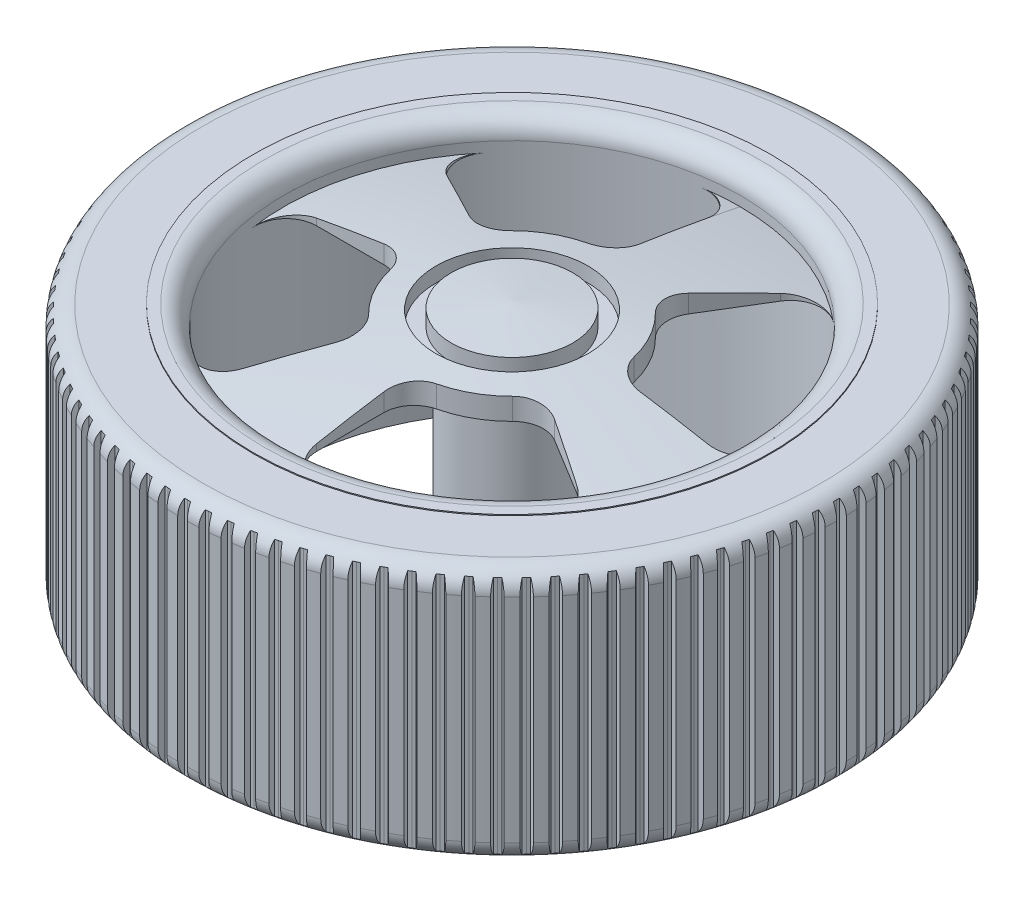
SolidWorks part; units mm, degrees
ref_plane "Ön Düzlem" through (0, 0, 0) normal (0, 0, 1) x (1, 0, 0)
ref_plane "Üst Düzlem" through (0, 0, 0) normal (0, 1, 0) x (1, 0, 0)
ref_plane "Sağ Düzlem" through (0, 0, 0) normal (1, 0, 0) x (0, 0, -1)
sketch "Çizim1" plane through (0, 0, 0) normal (0, 1, 0) x (1, 0, 0)
  circle A0 centre (0, 0) radius 32.5
  circle A1 centre (0, 0) radius 25.5
  dimension "D1" = 65
  dimension "D2" = 51
extrude "Yükseklik-Ekstrüzyon1" add sketch "Çizim1" along normal blind 12.5 and the other way blind 12.5
fillet "Radyus2" radius 2 2 edges at (0, 12.5, 32.5) (0, -12.5, 32.5)
sketch "Çizim2" plane through (0, 0, 0) normal (0, 1, 0) x (1, 0, 0)
  line L0 (0, 0) -> (0, 32) construction
  line L1 (0, 32) -> (-0.3, 31.9986)
  line L2 (-0.3, 31.9986) -> (-0.5822, 32.8175)
  line L3 (-0.5822, 32.8175) -> (0.5822, 32.8175)
  line L5 (0, 32) -> (0.3, 31.9986)
  line L6 (0.3, 31.9986) -> (0.5822, 32.8175)
  line L7 (2.0093, 31.9369) -> (2.3086, 31.9166)
  line L8 (2.3086, 31.9166) -> (2.6417, 32.7162)
  line L9 (1.4796, 32.7893) -> (2.6417, 32.7162)
  line L10 (1.7098, 31.9543) -> (1.4796, 32.7893)
  line L11 (2.0093, 31.9369) -> (1.7098, 31.9543)
  line L12 (4.0107, 31.7477) -> (4.3081, 31.7087)
  line L13 (4.3081, 31.7087) -> (4.6907, 32.4858)
  line L14 (3.5355, 32.6317) -> (4.6907, 32.4858)
  line L15 (3.7129, 31.7839) -> (3.5355, 32.6317)
  line L16 (4.0107, 31.7477) -> (3.7129, 31.7839)
  line L17 (5.9962, 31.4332) -> (6.2906, 31.3756)
  line L18 (6.2906, 31.3756) -> (6.7213, 32.1271)
  line L19 (5.5775, 32.3453) -> (6.7213, 32.1271)
  line L20 (5.7013, 31.488) -> (5.5775, 32.3453)
  line L21 (5.9962, 31.4332) -> (5.7013, 31.488)
  line L22 (7.9581, 30.9947) -> (8.2483, 30.9187)
  line L23 (8.2483, 30.9187) -> (8.7253, 31.6417)
  line L24 (7.5975, 31.9313) -> (8.7253, 31.6417)
  line L25 (7.6672, 31.0679) -> (7.5975, 31.9313)
  line L26 (7.9581, 30.9947) -> (7.6672, 31.0679)
  line L27 (9.8885, 30.4338) -> (10.1734, 30.3398)
  line L28 (10.1734, 30.3398) -> (10.6949, 31.0314)
  line L29 (9.5875, 31.3912) -> (10.6949, 31.0314)
  line L30 (9.6028, 30.5252) -> (9.5875, 31.3912)
  line L31 (9.8885, 30.4338) -> (9.6028, 30.5252)
  line L32 (11.78, 29.7528) -> (12.0584, 29.6411)
  line L33 (12.0584, 29.6411) -> (12.6222, 30.2986)
  line L34 (11.5396, 30.7273) -> (12.6222, 30.2986)
  line L35 (11.5005, 29.862) -> (11.5396, 30.7273)
  line L36 (11.78, 29.7528) -> (11.5005, 29.862)
  line L37 (13.6249, 28.9545) -> (13.8958, 28.8255)
  line L38 (13.8958, 28.8255) -> (14.4998, 29.4463)
  line L39 (13.4462, 29.942) -> (14.4998, 29.4463)
  line L40 (13.3529, 29.0809) -> (13.4462, 29.942)
  line L41 (13.6249, 28.9545) -> (13.3529, 29.0809)
  line L42 (15.4161, 28.0418) -> (15.6783, 27.8961)
  line L43 (15.6783, 27.8961) -> (16.3201, 28.4777)
  line L44 (15.2998, 29.0387) -> (16.3201, 28.4777)
  line L45 (15.1525, 28.1851) -> (15.2998, 29.0387)
  line L46 (15.4161, 28.0418) -> (15.1525, 28.1851)
  line L47 (17.1465, 27.0185) -> (17.399, 26.8566)
  line L48 (17.399, 26.8566) -> (18.0761, 27.3968)
  line L49 (17.0929, 28.0207) -> (18.0761, 27.3968)
  line L50 (16.8924, 27.1781) -> (17.0929, 28.0207)
  line L51 (17.1465, 27.0185) -> (16.8924, 27.1781)
  line L52 (18.8091, 25.8885) -> (19.051, 25.7111)
  line L53 (19.051, 25.7111) -> (19.7606, 26.2077)
  line L54 (18.8186, 26.8921) -> (19.7606, 26.2077)
  line L55 (18.5656, 26.0637) -> (18.8186, 26.8921)
  line L56 (18.8091, 25.8885) -> (18.5656, 26.0637)
  line L57 (20.3976, 24.6564) -> (20.6278, 24.4641)
  line L58 (20.6278, 24.4641) -> (21.3672, 24.9152)
  line L59 (20.4701, 25.6574) -> (21.3672, 24.9152)
  line L60 (20.1655, 24.8466) -> (20.4701, 25.6574)
  line L61 (20.3976, 24.6564) -> (20.1655, 24.8466)
  line L62 (21.9055, 23.327) -> (22.1232, 23.1206)
  line L63 (22.1232, 23.1206) -> (22.8895, 23.5244)
  line L64 (22.0407, 24.3215) -> (22.8895, 23.5244)
  line L65 (21.6859, 23.5313) -> (22.0407, 24.3215)
  line L66 (21.9055, 23.327) -> (21.6859, 23.5313)
  line L67 (23.327, 21.9055) -> (23.5313, 21.6859)
  line L68 (23.5313, 21.6859) -> (24.3215, 22.0407)
  line L69 (23.5244, 22.8895) -> (24.3215, 22.0407)
  line L70 (23.1206, 22.1232) -> (23.5244, 22.8895)
  line L71 (23.327, 21.9055) -> (23.1206, 22.1232)
  line L72 (24.6564, 20.3976) -> (24.8466, 20.1655)
  line L73 (24.8466, 20.1655) -> (25.6574, 20.4701)
  line L74 (24.9152, 21.3672) -> (25.6574, 20.4701)
  line L75 (24.4641, 20.6278) -> (24.9152, 21.3672)
  line L76 (24.6564, 20.3976) -> (24.4641, 20.6278)
  line L77 (25.8885, 18.8091) -> (26.0637, 18.5656)
  line L78 (26.0637, 18.5656) -> (26.8921, 18.8186)
  line L79 (26.2077, 19.7606) -> (26.8921, 18.8186)
  line L80 (25.7111, 19.051) -> (26.2077, 19.7606)
  line L81 (25.8885, 18.8091) -> (25.7111, 19.051)
  line L82 (27.0185, 17.1465) -> (27.1781, 16.8924)
  line L83 (27.1781, 16.8924) -> (28.0207, 17.0929)
  line L84 (27.3968, 18.0761) -> (28.0207, 17.0929)
  line L85 (26.8566, 17.399) -> (27.3968, 18.0761)
  line L86 (27.0185, 17.1465) -> (26.8566, 17.399)
  line L87 (28.0418, 15.4161) -> (28.1851, 15.1525)
  line L88 (28.1851, 15.1525) -> (29.0387, 15.2998)
  line L89 (28.4777, 16.3201) -> (29.0387, 15.2998)
  line L90 (27.8961, 15.6783) -> (28.4777, 16.3201)
  line L91 (28.0418, 15.4161) -> (27.8961, 15.6783)
  line L92 (28.9545, 13.6249) -> (29.0809, 13.3529)
  line L93 (29.0809, 13.3529) -> (29.942, 13.4462)
  line L94 (29.4463, 14.4998) -> (29.942, 13.4462)
  line L95 (28.8255, 13.8958) -> (29.4463, 14.4998)
  line L96 (28.9545, 13.6249) -> (28.8255, 13.8958)
  line L97 (29.7528, 11.78) -> (29.862, 11.5005)
  line L98 (29.862, 11.5005) -> (30.7273, 11.5396)
  line L99 (30.2986, 12.6222) -> (30.7273, 11.5396)
  line L100 (29.6411, 12.0584) -> (30.2986, 12.6222)
  line L101 (29.7528, 11.78) -> (29.6411, 12.0584)
  line L102 (30.4338, 9.8885) -> (30.5252, 9.6028)
  line L103 (30.5252, 9.6028) -> (31.3912, 9.5875)
  line L104 (31.0314, 10.6949) -> (31.3912, 9.5875)
  line L105 (30.3398, 10.1734) -> (31.0314, 10.6949)
  line L106 (30.4338, 9.8885) -> (30.3398, 10.1734)
  line L107 (30.9947, 7.9581) -> (31.0679, 7.6672)
  line L108 (31.0679, 7.6672) -> (31.9313, 7.5975)
  line L109 (31.6417, 8.7253) -> (31.9313, 7.5975)
  line L110 (30.9187, 8.2483) -> (31.6417, 8.7253)
  line L111 (30.9947, 7.9581) -> (30.9187, 8.2483)
  line L112 (31.4332, 5.9962) -> (31.488, 5.7013)
  line L113 (31.488, 5.7013) -> (32.3453, 5.5775)
  line L114 (32.1271, 6.7213) -> (32.3453, 5.5775)
  line L115 (31.3756, 6.2906) -> (32.1271, 6.7213)
  line L116 (31.4332, 5.9962) -> (31.3756, 6.2906)
  line L117 (31.7477, 4.0107) -> (31.7839, 3.7129)
  line L118 (31.7839, 3.7129) -> (32.6317, 3.5355)
  line L119 (32.4858, 4.6907) -> (32.6317, 3.5355)
  line L120 (31.7087, 4.3081) -> (32.4858, 4.6907)
  line L121 (31.7477, 4.0107) -> (31.7087, 4.3081)
  line L122 (31.9369, 2.0093) -> (31.9543, 1.7098)
  line L123 (31.9543, 1.7098) -> (32.7893, 1.4796)
  line L124 (32.7162, 2.6417) -> (32.7893, 1.4796)
  line L125 (31.9166, 2.3086) -> (32.7162, 2.6417)
  line L126 (31.9369, 2.0093) -> (31.9166, 2.3086)
  line L127 (32, 0) -> (31.9986, -0.3)
  line L128 (31.9986, -0.3) -> (32.8175, -0.5822)
  line L129 (32.8175, 0.5822) -> (32.8175, -0.5822)
  line L130 (31.9986, 0.3) -> (32.8175, 0.5822)
  line L131 (32, 0) -> (31.9986, 0.3)
  line L132 (31.9369, -2.0093) -> (31.9166, -2.3086)
  line L133 (31.9166, -2.3086) -> (32.7162, -2.6417)
  line L134 (32.7893, -1.4796) -> (32.7162, -2.6417)
  line L135 (31.9543, -1.7098) -> (32.7893, -1.4796)
  line L136 (31.9369, -2.0093) -> (31.9543, -1.7098)
  line L137 (31.7477, -4.0107) -> (31.7087, -4.3081)
  line L138 (31.7087, -4.3081) -> (32.4858, -4.6907)
  line L139 (32.6317, -3.5355) -> (32.4858, -4.6907)
  line L140 (31.7839, -3.7129) -> (32.6317, -3.5355)
  line L141 (31.7477, -4.0107) -> (31.7839, -3.7129)
  line L142 (31.4332, -5.9962) -> (31.3756, -6.2906)
  line L143 (31.3756, -6.2906) -> (32.1271, -6.7213)
  line L144 (32.3453, -5.5775) -> (32.1271, -6.7213)
  line L145 (31.488, -5.7013) -> (32.3453, -5.5775)
  line L146 (31.4332, -5.9962) -> (31.488, -5.7013)
  line L147 (30.9947, -7.9581) -> (30.9187, -8.2483)
  line L148 (30.9187, -8.2483) -> (31.6417, -8.7253)
  line L149 (31.9313, -7.5975) -> (31.6417, -8.7253)
  line L150 (31.0679, -7.6672) -> (31.9313, -7.5975)
  line L151 (30.9947, -7.9581) -> (31.0679, -7.6672)
  line L152 (30.4338, -9.8885) -> (30.3398, -10.1734)
  line L153 (30.3398, -10.1734) -> (31.0314, -10.6949)
  line L154 (31.3912, -9.5875) -> (31.0314, -10.6949)
  line L155 (30.5252, -9.6028) -> (31.3912, -9.5875)
  line L156 (30.4338, -9.8885) -> (30.5252, -9.6028)
  line L157 (29.7528, -11.78) -> (29.6411, -12.0584)
  line L158 (29.6411, -12.0584) -> (30.2986, -12.6222)
  line L159 (30.7273, -11.5396) -> (30.2986, -12.6222)
  line L160 (29.862, -11.5005) -> (30.7273, -11.5396)
  line L161 (29.7528, -11.78) -> (29.862, -11.5005)
  line L162 (28.9545, -13.6249) -> (28.8255, -13.8958)
  line L163 (28.8255, -13.8958) -> (29.4463, -14.4998)
  line L164 (29.942, -13.4462) -> (29.4463, -14.4998)
  line L165 (29.0809, -13.3529) -> (29.942, -13.4462)
  line L166 (28.9545, -13.6249) -> (29.0809, -13.3529)
  line L167 (28.0418, -15.4161) -> (27.8961, -15.6783)
  line L168 (27.8961, -15.6783) -> (28.4777, -16.3201)
  line L169 (29.0387, -15.2998) -> (28.4777, -16.3201)
  line L170 (28.1851, -15.1525) -> (29.0387, -15.2998)
  line L171 (28.0418, -15.4161) -> (28.1851, -15.1525)
  line L172 (27.0185, -17.1465) -> (26.8566, -17.399)
  line L173 (26.8566, -17.399) -> (27.3968, -18.0761)
  line L174 (28.0207, -17.0929) -> (27.3968, -18.0761)
  line L175 (27.1781, -16.8924) -> (28.0207, -17.0929)
  line L176 (27.0185, -17.1465) -> (27.1781, -16.8924)
  line L177 (25.8885, -18.8091) -> (25.7111, -19.051)
  line L178 (25.7111, -19.051) -> (26.2077, -19.7606)
  line L179 (26.8921, -18.8186) -> (26.2077, -19.7606)
  line L180 (26.0637, -18.5656) -> (26.8921, -18.8186)
  line L181 (25.8885, -18.8091) -> (26.0637, -18.5656)
  line L182 (24.6564, -20.3976) -> (24.4641, -20.6278)
  line L183 (24.4641, -20.6278) -> (24.9152, -21.3672)
  line L184 (25.6574, -20.4701) -> (24.9152, -21.3672)
  line L185 (24.8466, -20.1655) -> (25.6574, -20.4701)
  line L186 (24.6564, -20.3976) -> (24.8466, -20.1655)
  line L187 (23.327, -21.9055) -> (23.1206, -22.1232)
  line L188 (23.1206, -22.1232) -> (23.5244, -22.8895)
  line L189 (24.3215, -22.0407) -> (23.5244, -22.8895)
  line L190 (23.5313, -21.6859) -> (24.3215, -22.0407)
  line L191 (23.327, -21.9055) -> (23.5313, -21.6859)
  line L192 (21.9055, -23.327) -> (21.6859, -23.5313)
  line L193 (21.6859, -23.5313) -> (22.0407, -24.3215)
  line L194 (22.8895, -23.5244) -> (22.0407, -24.3215)
  line L195 (22.1232, -23.1206) -> (22.8895, -23.5244)
  line L196 (21.9055, -23.327) -> (22.1232, -23.1206)
  line L197 (20.3976, -24.6564) -> (20.1655, -24.8466)
  line L198 (20.1655, -24.8466) -> (20.4701, -25.6574)
  line L199 (21.3672, -24.9152) -> (20.4701, -25.6574)
  line L200 (20.6278, -24.4641) -> (21.3672, -24.9152)
  line L201 (20.3976, -24.6564) -> (20.6278, -24.4641)
  line L202 (18.8091, -25.8885) -> (18.5656, -26.0637)
  line L203 (18.5656, -26.0637) -> (18.8186, -26.8921)
  line L204 (19.7606, -26.2077) -> (18.8186, -26.8921)
  line L205 (19.051, -25.7111) -> (19.7606, -26.2077)
  line L206 (18.8091, -25.8885) -> (19.051, -25.7111)
  line L207 (17.1465, -27.0185) -> (16.8924, -27.1781)
  line L208 (16.8924, -27.1781) -> (17.0929, -28.0207)
  line L209 (18.0761, -27.3968) -> (17.0929, -28.0207)
  line L210 (17.399, -26.8566) -> (18.0761, -27.3968)
  line L211 (17.1465, -27.0185) -> (17.399, -26.8566)
  line L212 (15.4161, -28.0418) -> (15.1525, -28.1851)
  line L213 (15.1525, -28.1851) -> (15.2998, -29.0387)
  line L214 (16.3201, -28.4777) -> (15.2998, -29.0387)
  line L215 (15.6783, -27.8961) -> (16.3201, -28.4777)
  line L216 (15.4161, -28.0418) -> (15.6783, -27.8961)
  line L217 (13.6249, -28.9545) -> (13.3529, -29.0809)
  line L218 (13.3529, -29.0809) -> (13.4462, -29.942)
  line L219 (14.4998, -29.4463) -> (13.4462, -29.942)
  line L220 (13.8958, -28.8255) -> (14.4998, -29.4463)
  line L221 (13.6249, -28.9545) -> (13.8958, -28.8255)
  line L222 (11.78, -29.7528) -> (11.5005, -29.862)
  line L223 (11.5005, -29.862) -> (11.5396, -30.7273)
  line L224 (12.6222, -30.2986) -> (11.5396, -30.7273)
  line L225 (12.0584, -29.6411) -> (12.6222, -30.2986)
  line L226 (11.78, -29.7528) -> (12.0584, -29.6411)
  line L227 (9.8885, -30.4338) -> (9.6028, -30.5252)
  line L228 (9.6028, -30.5252) -> (9.5875, -31.3912)
  line L229 (10.6949, -31.0314) -> (9.5875, -31.3912)
  line L230 (10.1734, -30.3398) -> (10.6949, -31.0314)
  line L231 (9.8885, -30.4338) -> (10.1734, -30.3398)
  line L232 (7.9581, -30.9947) -> (7.6672, -31.0679)
  line L233 (7.6672, -31.0679) -> (7.5975, -31.9313)
  line L234 (8.7253, -31.6417) -> (7.5975, -31.9313)
  line L235 (8.2483, -30.9187) -> (8.7253, -31.6417)
  line L236 (7.9581, -30.9947) -> (8.2483, -30.9187)
  line L237 (5.9962, -31.4332) -> (5.7013, -31.488)
  line L238 (5.7013, -31.488) -> (5.5775, -32.3453)
  line L239 (6.7213, -32.1271) -> (5.5775, -32.3453)
  line L240 (6.2906, -31.3756) -> (6.7213, -32.1271)
  line L241 (5.9962, -31.4332) -> (6.2906, -31.3756)
  line L242 (4.0107, -31.7477) -> (3.7129, -31.7839)
  line L243 (3.7129, -31.7839) -> (3.5355, -32.6317)
  line L244 (4.6907, -32.4858) -> (3.5355, -32.6317)
  line L245 (4.3081, -31.7087) -> (4.6907, -32.4858)
  line L246 (4.0107, -31.7477) -> (4.3081, -31.7087)
  line L247 (2.0093, -31.9369) -> (1.7098, -31.9543)
  line L248 (1.7098, -31.9543) -> (1.4796, -32.7893)
  line L249 (2.6417, -32.7162) -> (1.4796, -32.7893)
  line L250 (2.3086, -31.9166) -> (2.6417, -32.7162)
  line L251 (2.0093, -31.9369) -> (2.3086, -31.9166)
  line L252 (0, -32) -> (-0.3, -31.9986)
  line L253 (-0.3, -31.9986) -> (-0.5822, -32.8175)
  line L254 (0.5822, -32.8175) -> (-0.5822, -32.8175)
  line L255 (0.3, -31.9986) -> (0.5822, -32.8175)
  line L256 (0, -32) -> (0.3, -31.9986)
  line L257 (-2.0093, -31.9369) -> (-2.3086, -31.9166)
  line L258 (-2.3086, -31.9166) -> (-2.6417, -32.7162)
  line L259 (-1.4796, -32.7893) -> (-2.6417, -32.7162)
  line L260 (-1.7098, -31.9543) -> (-1.4796, -32.7893)
  line L261 (-2.0093, -31.9369) -> (-1.7098, -31.9543)
  line L262 (-4.0107, -31.7477) -> (-4.3081, -31.7087)
  line L263 (-4.3081, -31.7087) -> (-4.6907, -32.4858)
  line L264 (-3.5355, -32.6317) -> (-4.6907, -32.4858)
  line L265 (-3.7129, -31.7839) -> (-3.5355, -32.6317)
  line L266 (-4.0107, -31.7477) -> (-3.7129, -31.7839)
  line L267 (-5.9962, -31.4332) -> (-6.2906, -31.3756)
  line L268 (-6.2906, -31.3756) -> (-6.7213, -32.1271)
  line L269 (-5.5775, -32.3453) -> (-6.7213, -32.1271)
  line L270 (-5.7013, -31.488) -> (-5.5775, -32.3453)
  line L271 (-5.9962, -31.4332) -> (-5.7013, -31.488)
  line L272 (-7.9581, -30.9947) -> (-8.2483, -30.9187)
  line L273 (-8.2483, -30.9187) -> (-8.7253, -31.6417)
  line L274 (-7.5975, -31.9313) -> (-8.7253, -31.6417)
  line L275 (-7.6672, -31.0679) -> (-7.5975, -31.9313)
  line L276 (-7.9581, -30.9947) -> (-7.6672, -31.0679)
  line L277 (-9.8885, -30.4338) -> (-10.1734, -30.3398)
  line L278 (-10.1734, -30.3398) -> (-10.6949, -31.0314)
  line L279 (-9.5875, -31.3912) -> (-10.6949, -31.0314)
  line L280 (-9.6028, -30.5252) -> (-9.5875, -31.3912)
  line L281 (-9.8885, -30.4338) -> (-9.6028, -30.5252)
  line L282 (-11.78, -29.7528) -> (-12.0584, -29.6411)
  line L283 (-12.0584, -29.6411) -> (-12.6222, -30.2986)
  line L284 (-11.5396, -30.7273) -> (-12.6222, -30.2986)
  line L285 (-11.5005, -29.862) -> (-11.5396, -30.7273)
  line L286 (-11.78, -29.7528) -> (-11.5005, -29.862)
  line L287 (-13.6249, -28.9545) -> (-13.8958, -28.8255)
  line L288 (-13.8958, -28.8255) -> (-14.4998, -29.4463)
  line L289 (-13.4462, -29.942) -> (-14.4998, -29.4463)
  line L290 (-13.3529, -29.0809) -> (-13.4462, -29.942)
  line L291 (-13.6249, -28.9545) -> (-13.3529, -29.0809)
  line L292 (-15.4161, -28.0418) -> (-15.6783, -27.8961)
  line L293 (-15.6783, -27.8961) -> (-16.3201, -28.4777)
  line L294 (-15.2998, -29.0387) -> (-16.3201, -28.4777)
  line L295 (-15.1525, -28.1851) -> (-15.2998, -29.0387)
  line L296 (-15.4161, -28.0418) -> (-15.1525, -28.1851)
  line L297 (-17.1465, -27.0185) -> (-17.399, -26.8566)
  line L298 (-17.399, -26.8566) -> (-18.0761, -27.3968)
  line L299 (-17.0929, -28.0207) -> (-18.0761, -27.3968)
  line L300 (-16.8924, -27.1781) -> (-17.0929, -28.0207)
  line L301 (-17.1465, -27.0185) -> (-16.8924, -27.1781)
  line L302 (-18.8091, -25.8885) -> (-19.051, -25.7111)
  line L303 (-19.051, -25.7111) -> (-19.7606, -26.2077)
  line L304 (-18.8186, -26.8921) -> (-19.7606, -26.2077)
  line L305 (-18.5656, -26.0637) -> (-18.8186, -26.8921)
  line L306 (-18.8091, -25.8885) -> (-18.5656, -26.0637)
  line L307 (-20.3976, -24.6564) -> (-20.6278, -24.4641)
  line L308 (-20.6278, -24.4641) -> (-21.3672, -24.9152)
  line L309 (-20.4701, -25.6574) -> (-21.3672, -24.9152)
  line L310 (-20.1655, -24.8466) -> (-20.4701, -25.6574)
  line L311 (-20.3976, -24.6564) -> (-20.1655, -24.8466)
  line L312 (-21.9055, -23.327) -> (-22.1232, -23.1206)
  line L313 (-22.1232, -23.1206) -> (-22.8895, -23.5244)
  line L314 (-22.0407, -24.3215) -> (-22.8895, -23.5244)
  line L315 (-21.6859, -23.5313) -> (-22.0407, -24.3215)
  line L316 (-21.9055, -23.327) -> (-21.6859, -23.5313)
  line L317 (-23.327, -21.9055) -> (-23.5313, -21.6859)
  line L318 (-23.5313, -21.6859) -> (-24.3215, -22.0407)
  line L319 (-23.5244, -22.8895) -> (-24.3215, -22.0407)
  line L320 (-23.1206, -22.1232) -> (-23.5244, -22.8895)
  line L321 (-23.327, -21.9055) -> (-23.1206, -22.1232)
  line L322 (-24.6564, -20.3976) -> (-24.8466, -20.1655)
  line L323 (-24.8466, -20.1655) -> (-25.6574, -20.4701)
  line L324 (-24.9152, -21.3672) -> (-25.6574, -20.4701)
  line L325 (-24.4641, -20.6278) -> (-24.9152, -21.3672)
  line L326 (-24.6564, -20.3976) -> (-24.4641, -20.6278)
  line L327 (-25.8885, -18.8091) -> (-26.0637, -18.5656)
  line L328 (-26.0637, -18.5656) -> (-26.8921, -18.8186)
  line L329 (-26.2077, -19.7606) -> (-26.8921, -18.8186)
  line L330 (-25.7111, -19.051) -> (-26.2077, -19.7606)
  line L331 (-25.8885, -18.8091) -> (-25.7111, -19.051)
  line L332 (-27.0185, -17.1465) -> (-27.1781, -16.8924)
  line L333 (-27.1781, -16.8924) -> (-28.0207, -17.0929)
  line L334 (-27.3968, -18.0761) -> (-28.0207, -17.0929)
  line L335 (-26.8566, -17.399) -> (-27.3968, -18.0761)
  line L336 (-27.0185, -17.1465) -> (-26.8566, -17.399)
  line L337 (-28.0418, -15.4161) -> (-28.1851, -15.1525)
  line L338 (-28.1851, -15.1525) -> (-29.0387, -15.2998)
  line L339 (-28.4777, -16.3201) -> (-29.0387, -15.2998)
  line L340 (-27.8961, -15.6783) -> (-28.4777, -16.3201)
  line L341 (-28.0418, -15.4161) -> (-27.8961, -15.6783)
  line L342 (-28.9545, -13.6249) -> (-29.0809, -13.3529)
  line L343 (-29.0809, -13.3529) -> (-29.942, -13.4462)
  line L344 (-29.4463, -14.4998) -> (-29.942, -13.4462)
  line L345 (-28.8255, -13.8958) -> (-29.4463, -14.4998)
  line L346 (-28.9545, -13.6249) -> (-28.8255, -13.8958)
  line L347 (-29.7528, -11.78) -> (-29.862, -11.5005)
  line L348 (-29.862, -11.5005) -> (-30.7273, -11.5396)
  line L349 (-30.2986, -12.6222) -> (-30.7273, -11.5396)
  line L350 (-29.6411, -12.0584) -> (-30.2986, -12.6222)
  line L351 (-29.7528, -11.78) -> (-29.6411, -12.0584)
  line L352 (-30.4338, -9.8885) -> (-30.5252, -9.6028)
  line L353 (-30.5252, -9.6028) -> (-31.3912, -9.5875)
  line L354 (-31.0314, -10.6949) -> (-31.3912, -9.5875)
  line L355 (-30.3398, -10.1734) -> (-31.0314, -10.6949)
  line L356 (-30.4338, -9.8885) -> (-30.3398, -10.1734)
  line L357 (-30.9947, -7.9581) -> (-31.0679, -7.6672)
  line L358 (-31.0679, -7.6672) -> (-31.9313, -7.5975)
  line L359 (-31.6417, -8.7253) -> (-31.9313, -7.5975)
  line L360 (-30.9187, -8.2483) -> (-31.6417, -8.7253)
  line L361 (-30.9947, -7.9581) -> (-30.9187, -8.2483)
  line L362 (-31.4332, -5.9962) -> (-31.488, -5.7013)
  line L363 (-31.488, -5.7013) -> (-32.3453, -5.5775)
  line L364 (-32.1271, -6.7213) -> (-32.3453, -5.5775)
  line L365 (-31.3756, -6.2906) -> (-32.1271, -6.7213)
  line L366 (-31.4332, -5.9962) -> (-31.3756, -6.2906)
  line L367 (-31.7477, -4.0107) -> (-31.7839, -3.7129)
  line L368 (-31.7839, -3.7129) -> (-32.6317, -3.5355)
  line L369 (-32.4858, -4.6907) -> (-32.6317, -3.5355)
  line L370 (-31.7087, -4.3081) -> (-32.4858, -4.6907)
  line L371 (-31.7477, -4.0107) -> (-31.7087, -4.3081)
  line L372 (-31.9369, -2.0093) -> (-31.9543, -1.7098)
  line L373 (-31.9543, -1.7098) -> (-32.7893, -1.4796)
  line L374 (-32.7162, -2.6417) -> (-32.7893, -1.4796)
  line L375 (-31.9166, -2.3086) -> (-32.7162, -2.6417)
  line L376 (-31.9369, -2.0093) -> (-31.9166, -2.3086)
  line L377 (-32, 0) -> (-31.9986, 0.3)
  line L378 (-31.9986, 0.3) -> (-32.8175, 0.5822)
  line L379 (-32.8175, -0.5822) -> (-32.8175, 0.5822)
  line L380 (-31.9986, -0.3) -> (-32.8175, -0.5822)
  line L381 (-32, 0) -> (-31.9986, -0.3)
  line L382 (-31.9369, 2.0093) -> (-31.9166, 2.3086)
  line L383 (-31.9166, 2.3086) -> (-32.7162, 2.6417)
  line L384 (-32.7893, 1.4796) -> (-32.7162, 2.6417)
  line L385 (-31.9543, 1.7098) -> (-32.7893, 1.4796)
  line L386 (-31.9369, 2.0093) -> (-31.9543, 1.7098)
  line L387 (-31.7477, 4.0107) -> (-31.7087, 4.3081)
  line L388 (-31.7087, 4.3081) -> (-32.4858, 4.6907)
  line L389 (-32.6317, 3.5355) -> (-32.4858, 4.6907)
  line L390 (-31.7839, 3.7129) -> (-32.6317, 3.5355)
  line L391 (-31.7477, 4.0107) -> (-31.7839, 3.7129)
  line L392 (-31.4332, 5.9962) -> (-31.3756, 6.2906)
  line L393 (-31.3756, 6.2906) -> (-32.1271, 6.7213)
  line L394 (-32.3453, 5.5775) -> (-32.1271, 6.7213)
  line L395 (-31.488, 5.7013) -> (-32.3453, 5.5775)
  line L396 (-31.4332, 5.9962) -> (-31.488, 5.7013)
  line L397 (-30.9947, 7.9581) -> (-30.9187, 8.2483)
  line L398 (-30.9187, 8.2483) -> (-31.6417, 8.7253)
  line L399 (-31.9313, 7.5975) -> (-31.6417, 8.7253)
  line L400 (-31.0679, 7.6672) -> (-31.9313, 7.5975)
  line L401 (-30.9947, 7.9581) -> (-31.0679, 7.6672)
  line L402 (-30.4338, 9.8885) -> (-30.3398, 10.1734)
  line L403 (-30.3398, 10.1734) -> (-31.0314, 10.6949)
  line L404 (-31.3912, 9.5875) -> (-31.0314, 10.6949)
  line L405 (-30.5252, 9.6028) -> (-31.3912, 9.5875)
  line L406 (-30.4338, 9.8885) -> (-30.5252, 9.6028)
  line L407 (-29.7528, 11.78) -> (-29.6411, 12.0584)
  line L408 (-29.6411, 12.0584) -> (-30.2986, 12.6222)
  line L409 (-30.7273, 11.5396) -> (-30.2986, 12.6222)
  line L410 (-29.862, 11.5005) -> (-30.7273, 11.5396)
  line L411 (-29.7528, 11.78) -> (-29.862, 11.5005)
  line L412 (-28.9545, 13.6249) -> (-28.8255, 13.8958)
  line L413 (-28.8255, 13.8958) -> (-29.4463, 14.4998)
  line L414 (-29.942, 13.4462) -> (-29.4463, 14.4998)
  line L415 (-29.0809, 13.3529) -> (-29.942, 13.4462)
  line L416 (-28.9545, 13.6249) -> (-29.0809, 13.3529)
  line L417 (-28.0418, 15.4161) -> (-27.8961, 15.6783)
  line L418 (-27.8961, 15.6783) -> (-28.4777, 16.3201)
  line L419 (-29.0387, 15.2998) -> (-28.4777, 16.3201)
  line L420 (-28.1851, 15.1525) -> (-29.0387, 15.2998)
  line L421 (-28.0418, 15.4161) -> (-28.1851, 15.1525)
  line L422 (-27.0185, 17.1465) -> (-26.8566, 17.399)
  line L423 (-26.8566, 17.399) -> (-27.3968, 18.0761)
  line L424 (-28.0207, 17.0929) -> (-27.3968, 18.0761)
  line L425 (-27.1781, 16.8924) -> (-28.0207, 17.0929)
  line L426 (-27.0185, 17.1465) -> (-27.1781, 16.8924)
  line L427 (-25.8885, 18.8091) -> (-25.7111, 19.051)
  line L428 (-25.7111, 19.051) -> (-26.2077, 19.7606)
  line L429 (-26.8921, 18.8186) -> (-26.2077, 19.7606)
  line L430 (-26.0637, 18.5656) -> (-26.8921, 18.8186)
  line L431 (-25.8885, 18.8091) -> (-26.0637, 18.5656)
  line L432 (-24.6564, 20.3976) -> (-24.4641, 20.6278)
  line L433 (-24.4641, 20.6278) -> (-24.9152, 21.3672)
  line L434 (-25.6574, 20.4701) -> (-24.9152, 21.3672)
  line L435 (-24.8466, 20.1655) -> (-25.6574, 20.4701)
  line L436 (-24.6564, 20.3976) -> (-24.8466, 20.1655)
  line L437 (-23.327, 21.9055) -> (-23.1206, 22.1232)
  line L438 (-23.1206, 22.1232) -> (-23.5244, 22.8895)
  line L439 (-24.3215, 22.0407) -> (-23.5244, 22.8895)
  line L440 (-23.5313, 21.6859) -> (-24.3215, 22.0407)
  line L441 (-23.327, 21.9055) -> (-23.5313, 21.6859)
  line L442 (-21.9055, 23.327) -> (-21.6859, 23.5313)
  line L443 (-21.6859, 23.5313) -> (-22.0407, 24.3215)
  line L444 (-22.8895, 23.5244) -> (-22.0407, 24.3215)
  line L445 (-22.1232, 23.1206) -> (-22.8895, 23.5244)
  line L446 (-21.9055, 23.327) -> (-22.1232, 23.1206)
  line L447 (-20.3976, 24.6564) -> (-20.1655, 24.8466)
  line L448 (-20.1655, 24.8466) -> (-20.4701, 25.6574)
  line L449 (-21.3672, 24.9152) -> (-20.4701, 25.6574)
  line L450 (-20.6278, 24.4641) -> (-21.3672, 24.9152)
  line L451 (-20.3976, 24.6564) -> (-20.6278, 24.4641)
  line L452 (-18.8091, 25.8885) -> (-18.5656, 26.0637)
  line L453 (-18.5656, 26.0637) -> (-18.8186, 26.8921)
  line L454 (-19.7606, 26.2077) -> (-18.8186, 26.8921)
  line L455 (-19.051, 25.7111) -> (-19.7606, 26.2077)
  line L456 (-18.8091, 25.8885) -> (-19.051, 25.7111)
  line L457 (-17.1465, 27.0185) -> (-16.8924, 27.1781)
  line L458 (-16.8924, 27.1781) -> (-17.0929, 28.0207)
  line L459 (-18.0761, 27.3968) -> (-17.0929, 28.0207)
  line L460 (-17.399, 26.8566) -> (-18.0761, 27.3968)
  line L461 (-17.1465, 27.0185) -> (-17.399, 26.8566)
  line L462 (-15.4161, 28.0418) -> (-15.1525, 28.1851)
  line L463 (-15.1525, 28.1851) -> (-15.2998, 29.0387)
  line L464 (-16.3201, 28.4777) -> (-15.2998, 29.0387)
  line L465 (-15.6783, 27.8961) -> (-16.3201, 28.4777)
  line L466 (-15.4161, 28.0418) -> (-15.6783, 27.8961)
  line L467 (-13.6249, 28.9545) -> (-13.3529, 29.0809)
  line L468 (-13.3529, 29.0809) -> (-13.4462, 29.942)
  line L469 (-14.4998, 29.4463) -> (-13.4462, 29.942)
  line L470 (-13.8958, 28.8255) -> (-14.4998, 29.4463)
  line L471 (-13.6249, 28.9545) -> (-13.8958, 28.8255)
  line L472 (-11.78, 29.7528) -> (-11.5005, 29.862)
  line L473 (-11.5005, 29.862) -> (-11.5396, 30.7273)
  line L474 (-12.6222, 30.2986) -> (-11.5396, 30.7273)
  line L475 (-12.0584, 29.6411) -> (-12.6222, 30.2986)
  line L476 (-11.78, 29.7528) -> (-12.0584, 29.6411)
  line L477 (-9.8885, 30.4338) -> (-9.6028, 30.5252)
  line L478 (-9.6028, 30.5252) -> (-9.5875, 31.3912)
  line L479 (-10.6949, 31.0314) -> (-9.5875, 31.3912)
  line L480 (-10.1734, 30.3398) -> (-10.6949, 31.0314)
  line L481 (-9.8885, 30.4338) -> (-10.1734, 30.3398)
  line L482 (-7.9581, 30.9947) -> (-7.6672, 31.0679)
  line L483 (-7.6672, 31.0679) -> (-7.5975, 31.9313)
  line L484 (-8.7253, 31.6417) -> (-7.5975, 31.9313)
  line L485 (-8.2483, 30.9187) -> (-8.7253, 31.6417)
  line L486 (-7.9581, 30.9947) -> (-8.2483, 30.9187)
  line L487 (-5.9962, 31.4332) -> (-5.7013, 31.488)
  line L488 (-5.7013, 31.488) -> (-5.5775, 32.3453)
  line L489 (-6.7213, 32.1271) -> (-5.5775, 32.3453)
  line L490 (-6.2906, 31.3756) -> (-6.7213, 32.1271)
  line L491 (-5.9962, 31.4332) -> (-6.2906, 31.3756)
  line L492 (-4.0107, 31.7477) -> (-3.7129, 31.7839)
  line L493 (-3.7129, 31.7839) -> (-3.5355, 32.6317)
  line L494 (-4.6907, 32.4858) -> (-3.5355, 32.6317)
  line L495 (-4.3081, 31.7087) -> (-4.6907, 32.4858)
  line L496 (-4.0107, 31.7477) -> (-4.3081, 31.7087)
  line L497 (-2.0093, 31.9369) -> (-1.7098, 31.9543)
  line L498 (-1.7098, 31.9543) -> (-1.4796, 32.7893)
  line L499 (-2.6417, 32.7162) -> (-1.4796, 32.7893)
  line L500 (-2.3086, 31.9166) -> (-2.6417, 32.7162)
  line L501 (-2.0093, 31.9369) -> (-2.3086, 31.9166)
  circle A0 centre (0, 0) radius 32.5 construction
  circle A1 centre (0, 0) radius 32 construction
  point P9 (0, 32.8175)
  point P508 (0, 0)
  dimension "D1" = 64
  dimension "D2" = 0.3
  dimension "D3" = 100
extrude "Kes-Ekstrüzyon1" cut sketch "Çizim2" against normal blind 12.5 and the other way blind 12.5
sketch "Çizim3" plane through (0, 0, 0) normal (0, 1, 0) x (1, 0, 0)
  line L0 (0, 0) -> (0, 3) construction
  line L1 (0, 3) -> (0, -3) construction
  line L2 (2, 2.2361) -> (2, -2.2361)
  line L3 (-2, 2.2361) -> (-2, -2.2361)
  circle A0 centre (0, 0) radius 5.5
  arc A1 (-2, -2.2361) -> (2, -2.2361) centre (0, 0) ccw
  arc A2 (2, 2.2361) -> (-2, 2.2361) centre (0, 0) ccw
  dimension "D1" = 11
  dimension "D2" = 6
  dimension "D3" = 2
extrude "Yükseklik-Ekstrüzyon2" add sketch "Çizim3" along normal blind 12 and the other way blind 15.5 separate body
sketch "Çizim4" plane through (0, 0, 0) normal (0, 1, 0) x (1, 0, 0)
  circle A0 centre (0, 0) radius 22.5
  circle A1 centre (0, 0) radius 25.5
  dimension "D1" = 45
extrude "Yükseklik-Ekstrüzyon3" add sketch "Çizim4" along normal blind 12.6 and the other way blind 12.6
sketch "Çizim5" plane through (0, 0, 0) normal (0, 0, 1) x (1, 0, 0)
  line L0 (0, 0) -> (0, 12.7781) construction
  line L1 (0, 9.6) -> (-22.5892, 9.6)
  line L2 (-22.5892, 10.5) -> (-22.5892, -10.5) construction
  line L3 (22.5, 12.6) -> (-22.5, 12.6) construction
  line L4 (0, 9.6) -> (0, 12.7781)
  spline S0 degree 2 poles (0, 12.7781) (-11.4526, 11.9299) (-22.5892, 9.6) knots 0 0 0 0.472837 0.472837 0.472837
  dimension "D1" = 3
revolve "Döndür1" add sketch "Çizim5" angle 360 about L0
sketch "Çizim6" plane through (0, 0, 0) normal (0, 1, 0) x (1, 0, 0)
  line L0 (0, 19.2678) -> (0, 12.6491)
  line L1 (-16.4464, 10.0382) -> (-10.7969, 6.59)
  line L2 (10.0382, 16.4464) -> (6.59, 10.7969)
  line L3 (19.2678, 0) -> (12.6491, 0)
  line L4 (16.4464, -10.0382) -> (10.7969, -6.59)
  line L5 (0, -19.2678) -> (0, -12.6491)
  line L6 (-10.0382, -16.4464) -> (-6.59, -10.7969)
  line L7 (-19.2678, 0) -> (-12.6491, 0)
  arc A0 (-3.4615, 22.2321) -> (-17.1732, 14.5372) centre (0, 0) ccw
  arc A1 (-2.3077, 9.7301) -> (-7.103, 7.039) centre (0, 0) ccw
  arc A2 (-16.4464, 10.0382) -> (-17.1732, 14.5372) centre (-14.8834, 12.5989) cw
  arc A3 (0, 19.2678) -> (-3.4615, 22.2321) centre (-3, 19.2678) ccw
  arc A4 (0, 12.6491) -> (-2.3077, 9.7301) centre (-3, 12.6491) cw
  arc A5 (-10.7969, 6.59) -> (-7.103, 7.039) centre (-9.2339, 9.1507) ccw
  arc A6 (9.7301, 2.3077) -> (7.039, 7.103) centre (0, 0) ccw
  arc A7 (6.59, 10.7969) -> (7.039, 7.103) centre (9.1507, 9.2339) ccw
  arc A8 (12.6491, 0) -> (9.7301, 2.3077) centre (12.6491, 3) cw
  arc A9 (10.0382, 16.4464) -> (14.5372, 17.1732) centre (12.5989, 14.8834) cw
  arc A10 (22.2321, 3.4615) -> (14.5372, 17.1732) centre (0, 0) ccw
  arc A11 (19.2678, 0) -> (22.2321, 3.4615) centre (19.2678, 3) ccw
  arc A12 (2.3077, -9.7301) -> (7.103, -7.039) centre (0, 0) ccw
  arc A13 (10.7969, -6.59) -> (7.103, -7.039) centre (9.2339, -9.1507) ccw
  arc A14 (0, -12.6491) -> (2.3077, -9.7301) centre (3, -12.6491) cw
  arc A15 (16.4464, -10.0382) -> (17.1732, -14.5372) centre (14.8834, -12.5989) cw
  arc A16 (3.4615, -22.2321) -> (17.1732, -14.5372) centre (0, 0) ccw
  arc A17 (0, -19.2678) -> (3.4615, -22.2321) centre (3, -19.2678) ccw
  arc A18 (-9.7301, -2.3077) -> (-7.039, -7.103) centre (0, 0) ccw
  arc A19 (-6.59, -10.7969) -> (-7.039, -7.103) centre (-9.1507, -9.2339) ccw
  arc A20 (-12.6491, 0) -> (-9.7301, -2.3077) centre (-12.6491, -3) cw
  arc A21 (-10.0382, -16.4464) -> (-14.5372, -17.1732) centre (-12.5989, -14.8834) cw
  arc A22 (-22.2321, -3.4615) -> (-14.5372, -17.1732) centre (0, 0) ccw
  arc A23 (-19.2678, 0) -> (-22.2321, -3.4615) centre (-19.2678, -3) ccw
  point P10 (0, 22.5)
  point P13 (0, 10)
  point P55 (0, 0)
  dimension "D1" = 20
  dimension "D2" = 3
  dimension "D3" = 4
extrude "Kes-Ekstrüzyon4" cut sketch "Çizim6" along normal blind 12.5
sketch "Çizim7" plane through (0, 12.6, 0) normal (0, 1, 0) x (1, 0, 0)
  circle A0 centre (0, 0) radius 7.5
  circle A1 centre (0, 0) radius 6
  dimension "D1" = 12
  dimension "D2" = 15
extrude "Kes-Ekstrüzyon6" cut sketch "Çizim7" against normal blind 2
fillet "Radyus3" radius 2 1 edges at (0, 12.6, 22.5)
